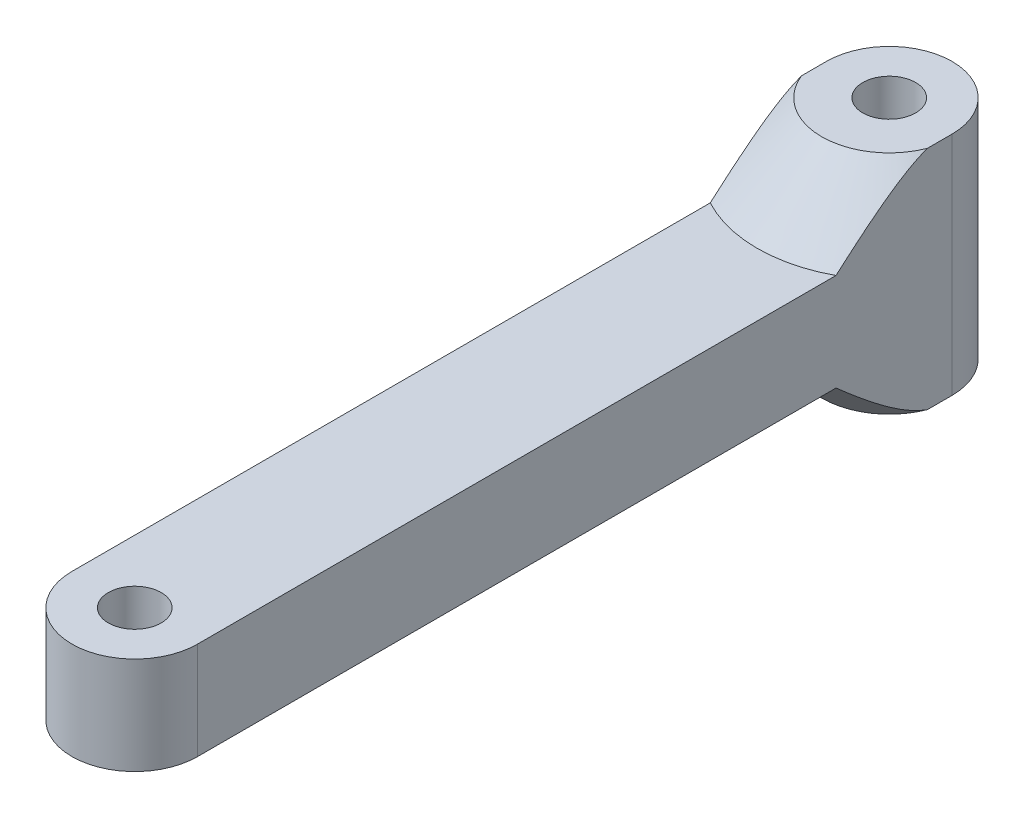
SolidWorks part; units mm, degrees
ref_plane "Plan de face" through (0, 0, 0) normal (0, 0, 1) x (1, 0, 0)
ref_plane "Plan de dessus" through (0, 0, 0) normal (0, 1, 0) x (1, 0, 0)
ref_plane "Plan de droite" through (0, 0, 0) normal (1, 0, 0) x (0, 0, -1)
sketch "Esquisse1" plane through (0, 0, 0) normal (0, 1, 0) x (1, 0, 0)
  line L0 (0, 0) -> (0, 60) construction
  line L1 (-5, 0) -> (-5, 60)
  line L2 (5, 0) -> (5, 60)
  arc A0 (-5, 0) -> (5, 0) centre (0, 0) ccw
  arc A1 (5, 60) -> (-5, 60) centre (0, 60) ccw
  circle A2 centre (0, 60) radius 2.1
  circle A3 centre (0, 0) radius 2.1
  point P3 (0, 30)
  dimension "D3" = 4.2
  dimension "D4" = 4.2
  dimension "D1" = 10
  dimension "D2" = 60
extrude "Boss.-Extru.1" add sketch "Esquisse1" along normal mid plane 7.75
sketch "Esquisse2" plane through (0, 0, 0) normal (0, 1, 0) x (1, 0, 0)
  line L0 (5, 0) -> (5, 60) construction
  circle A0 centre (0, 60) radius 2.1
  circle A1 centre (0, 60) radius 5
  circle A2 centre (0, 60) radius 2.1 construction
extrude "Boss.-Extru.2" add sketch "Esquisse2" along normal mid plane 18
chamfer "Chanfrein1" distance 5.5 angle 45 2 edges at (0, -3.875, -55) (0, 3.875, -55)
